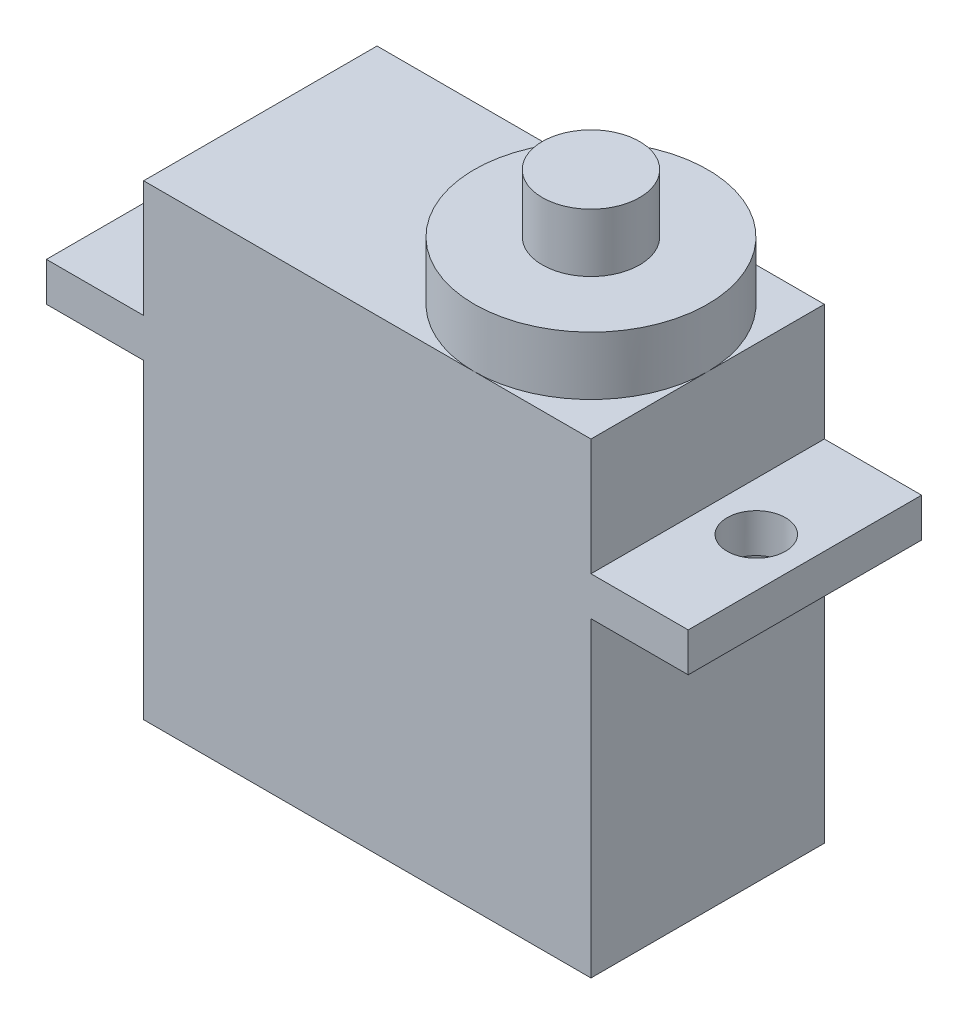
SolidWorks part; units mm, degrees
ref_plane "Front Plane" through (0, 0, 0) normal (0, 0, 1) x (1, 0, 0)
ref_plane "Top Plane" through (0, 0, 0) normal (0, 1, 0) x (1, 0, 0)
ref_plane "Right Plane" through (0, 0, 0) normal (1, 0, 0) x (0, 0, -1)
sketch "Sketch1" plane through (0, 0, 0) normal (0, 1, 0) x (1, 0, 0)
  line L1 (-11.5, -6) -> (11.5, -6)
  line L2 (-11.5, -6) -> (-11.5, 6)
  line L3 (-11.5, 6) -> (11.5, 6)
  line L4 (11.5, -6) -> (11.5, 6)
  line L5 (-11.5, -6) -> (11.5, 6) construction
  line L6 (-11.5, 6) -> (11.5, -6) construction
  point P0 (0, 0)
  dimension "D1" = 12
  dimension "D2" = 23
extrude "Boss-Extrude1" add sketch "Sketch1" along normal blind 24
sketch "Sketch2" plane through (-11.5, 0, 0) normal (-1, 0, 0) x (0, 0, 1)
  line L0 (-6, 24) -> (-6, 0) construction
  line L1 (-6, 18) -> (6, 18)
  line L2 (-6, 18) -> (-6, 16)
  line L3 (-6, 16) -> (6, 16)
  line L4 (6, 18) -> (6, 16)
  line L5 (6, 24) -> (6, 0) construction
  line L6 (-6, 0) -> (6, 0) construction
  dimension "D1" = 16
  dimension "D2" = 2
extrude "Boss-Extrude2" add sketch "Sketch2" along normal blind 5
sketch "Sketch3" plane through (0, 18, 0) normal (0, 1, 0) x (1, 0, 0)
  line L0 (-16.5, -6) -> (-16.5, 6) construction
  circle A0 centre (-14, 0) radius 1.5
  dimension "D1" = 2.5
  dimension "D2" = 3
extrude "Cut-Extrude1" cut sketch "Sketch3" against normal blind 5
mirror "Mirror1" about plane through (0, 0, 0) normal (1, 0, 0) of "Cut-Extrude1", "Boss-Extrude2"
sketch "Sketch4" plane through (0, 24, 0) normal (0, 1, 0) x (1, 0, 0)
  line L1 (11.5, -6) -> (11.5, 6) construction
  circle A0 centre (5.5, 0) radius 6
  dimension "D1" = 12
  dimension "D2" = 6
extrude "Boss-Extrude3" add sketch "Sketch4" along normal blind 3
sketch "Sketch5" plane through (0, 27, 0) normal (0, 1, 0) x (1, 0, 0)
  circle A0 centre (5.5, 0) radius 2.5
  circle A1 centre (5.5, 0) radius 6 construction
  dimension "D1" = 0
  dimension "D2" = 5
extrude "Boss-Extrude4" add sketch "Sketch5" along normal blind 3
